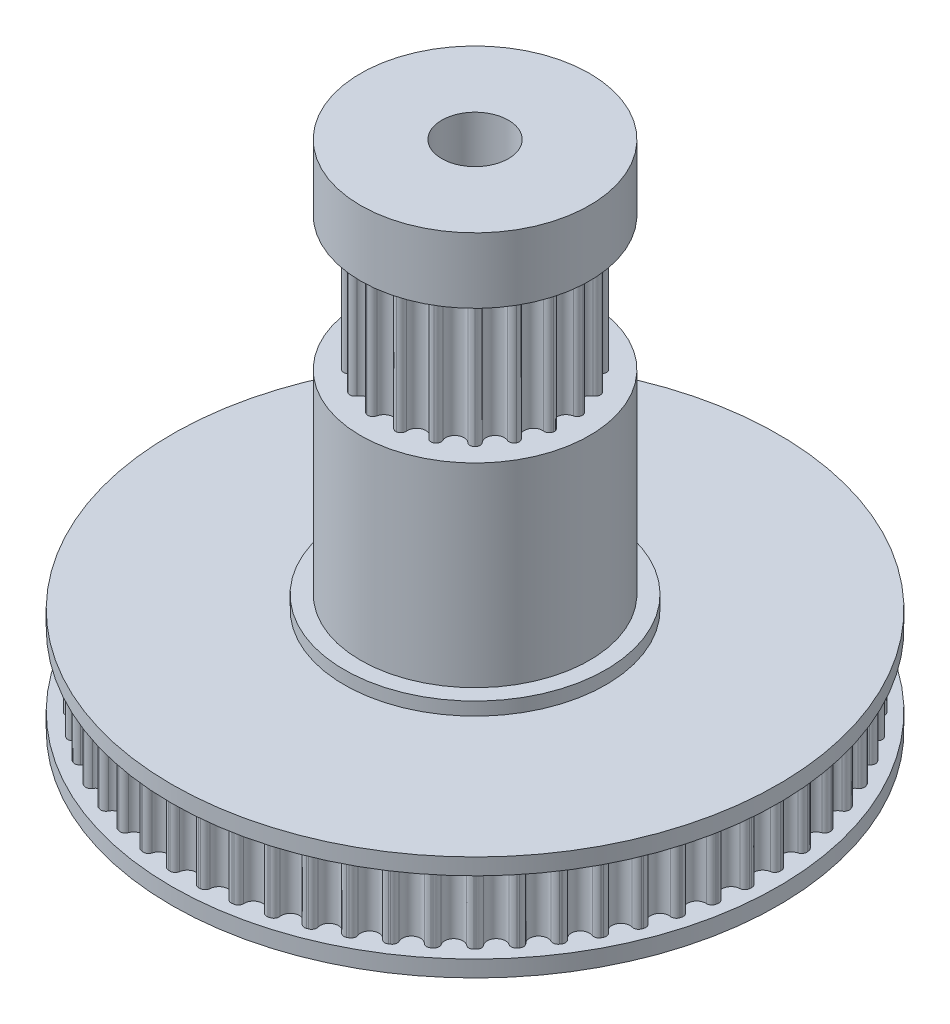
SolidWorks part; units mm, degrees
ref_plane "Front Plane" through (0, 0, 0) normal (0, 0, 1) x (1, 0, 0)
ref_plane "Top Plane" through (0, 0, 0) normal (0, 1, 0) x (1, 0, 0)
ref_plane "Right Plane" through (0, 0, 0) normal (1, 0, 0) x (0, 0, -1)
sketch "PulleyOffsets" plane through (0, 0, 0) normal (1, 0, 0) x (0, 0, -1)
  line L0 (15.875, 0) -> (-15.875, 0) construction
  line L1 (15.875, 31.75) -> (-15.875, 31.75) construction
  line L2 (0, 0) -> (0, 31.75) construction
  point P7 (0, 0)
  dimension "D1" = 31.75
ref_axis "Axis1" through (0, 34.9332, 0) along (0, -1, 0)
ref_plane "Big Pulley Plane" through (0, 0, 0) normal (0, 1, 0) x (1, 0, 0)
ref_plane "Small Pulley Plane" through (0, 31.75, 0) normal (0, 1, 0) x (1, 0, 0)
sketch "Sketch1" plane through (0, 0, 0) normal (0, 1, 0) x (1, 0, 0)
  line L0 (0, 0) -> (0, 28.2667) construction
  line L1 (0, 0) -> (2.9202, 27.7837) construction
  circle A0 centre (0, 0) radius 28.2667 construction
  circle A1 centre (0, 0) radius 27.0467 construction
  circle A2 centre (0, 27.9367) radius 0.89 construction
  circle A5 centre (2.9202, 27.7837) radius 0.89 construction
  arc A6 (0, 27.0467) -> (0.8804, 27.8061) centre (0, 27.9367) ccw
  arc A7 (0.8804, 27.8061) -> (1.3997, 28.2321) centre (1.3749, 27.7327) cw
  arc A8 (1.559, 28.2237) -> (2.031, 27.7458) centre (1.5314, 27.7245) cw
  arc A9 (2.8272, 26.8986) -> (2.031, 27.7458) centre (2.9202, 27.7837) cw
  arc A10 (1.3997, 28.2321) -> (1.559, 28.2237) centre (0, 0) cw
  arc A11 (0, 27.0467) -> (2.8272, 26.8986) centre (0, 0) ccw
  dimension "D1" = 56.5335
  dimension "D3" = 1.78
  dimension "D4" = 0.5
  dimension "D2" = 1.22
  dimension "D5" = 6
extrude "Boss-Extrude1" add sketch "Sketch1" along normal mid plane 7.112 contours A6 A11 A9 A8 A7 region at (0.001, 0, -0.0192)
pattern_circular "CirPattern1" count 60 over 360 about axis through (0, 34.9332, 0) along (0, -1, 0) of "Boss-Extrude1"
sketch "Sketch2" plane through (0, 0, 0) normal (1, 0, 0) x (0, 0, -1)
  line L10 (0, 3.5) -> (29.4415, 3.5) construction
  line L11 (0, 3.5) -> (0, 5.0875) construction
  line L12 (0, 5.0875) -> (29.4415, 5.0875) construction
  line L15 (29.4415, 3.5) -> (29.4415, 5.0875) construction
  line L20 (0, 34.9332) -> (0, -6.9932) construction
  line L22 (29.4415, 5.0875) -> (0, 5.0875)
  line L23 (29.4415, 5.0875) -> (29.4415, 3.5)
  line L24 (29.4415, 3.5) -> (0, 3.5)
  line L25 (0, 5.0875) -> (0, 3.5)
  dimension "D1" = 1.5875
  dimension "D2" = 29.4415
  dimension "D3" = 3.5
revolve "Revolve3" add sketch "Sketch2" angle 360 about axis through (0, 34.9332, 0) along (0, -1, 0) region at (0, 4.2937, -14.7207)
mirror "Mirror1" about plane through (0, 0, 0) normal (0, 1, 0) of "Revolve3"
sketch "Sketch3" plane through (0, 0, 0) normal (0, 1, 0) x (1, 0, 0)
  circle A0 centre (0, 0) radius 22.225
  dimension "D1" = 44.45
extrude "Cut-Extrude1" [suppressed] cut sketch "Sketch3" against normal through all both and the other way through all
sketch "Sketch6" plane through (0, 0, 0) normal (0, 1, 0) x (1, 0, 0)
  line L0 (0, 0) -> (0, 9.1676) construction
  line L1 (0, 0) -> (2.731, 8.405) construction
  circle A0 centre (0, 0) radius 9.1676 construction
  circle A1 centre (0, 0) radius 7.9476 construction
  circle A2 centre (0, 8.8376) radius 0.89 construction
  circle A5 centre (2.731, 8.405) radius 0.89 construction
  arc A6 (0, 7.9476) -> (0.8721, 8.6598) centre (0, 8.8376) ccw
  arc A7 (0.8721, 8.6598) -> (1.4405, 9.0537) centre (1.362, 8.5599) cw
  arc A8 (1.4277, 9.0557) -> (1.8466, 8.5054) centre (1.3498, 8.5618) cw
  arc A9 (2.4559, 7.5586) -> (1.8466, 8.5054) centre (2.731, 8.405) cw
  arc A10 (1.4405, 9.0537) -> (1.4277, 9.0557) centre (0, 0) cw construction
  arc A11 (0, 7.9476) -> (2.4559, 7.5586) centre (0, 0) ccw
  arc A12 (1.4405, 9.0537) -> (1.4277, 9.0557) centre (0, 0) cw
  dimension "D3" = 1.78
  dimension "D4" = 0.5
  dimension "D2" = 1.22
  dimension "D1" = 18.3352
  dimension "D5" = 18
extrude "Boss-Extrude2" add sketch "Sketch6" along normal mid plane 13 from surface contours A6 A11 A9 A8 A7 region at (0.0089, 0, -0.0564) starting at plane "Small Pulley Plane"
pattern_circular "CirPattern2" count 20 over 360 about axis through (0, 34.9332, 0) along (0, -1, 0) of "Boss-Extrude2"
sketch "Sketch4" plane through (0, 0, 0) normal (0, 0, 1) x (1, 0, 0)
  line L0 (12.7, 5.0875) -> (-12.7, 5.0875) construction
  line L1 (29.4415, 5.0875) -> (-29.4415, 5.0875) construction
  line L2 (-12.7, 5.0875) -> (-12.7, 6.3575)
  line L3 (-12.7, 6.3575) -> (-11.1125, 6.3575)
  line L4 (-11.1125, 6.3575) -> (-11.1125, 25.25)
  line L5 (0, 0) -> (0, 44.6) construction
  line L6 (11.1125, 6.3575) -> (11.1125, 25.25) construction
  line L7 (12.7, 6.3575) -> (11.1125, 6.3575) construction
  line L8 (12.7, 5.0875) -> (12.7, 6.3575) construction
  line L9 (-11.1125, 25.25) -> (11.1125, 25.25) construction
  line L10 (-12.7, 5.0875) -> (0, 5.0875)
  line L11 (0, 5.0875) -> (0, 25.25)
  line L12 (0, 25.25) -> (-11.1125, 25.25)
  line L13 (1.841, 25.25) -> (3.5054, 25.25) construction
  line L14 (0.8721, 38.25) -> (-0.8721, 38.25) construction
  line L15 (-11.1125, 44.6) -> (0, 44.6)
  line L16 (-11.1125, 44.6) -> (-11.1125, 38.25)
  line L17 (-11.1125, 38.25) -> (0, 38.25)
  line L18 (0, 44.6) -> (0, 38.25)
  line L19 (-11.1125, 25.25) -> (-11.1125, 38.25) construction
  point P14 (0, 5.0875)
  dimension "D1" = 1.27
  dimension "D2" = 25.4
  dimension "D3" = 22.225
  dimension "D4" = 6.35
revolve "Revolve4" add sketch "Sketch4" angle 360 about L11
sketch "Sketch7" plane through (0, 44.6, 0) normal (0, 1, 0) x (1, 0, 0)
  circle A0 centre (0, 0) radius 3.2385
  dimension "D1" = 6.477
extrude "Cut-Extrude2" cut sketch "Sketch7" against normal through all both and the other way through all
sketch "Sketch8" plane through (0, -5.0875, 0) normal (0, -1, 0) x (1, 0, 0)
  circle A0 centre (0, 0) radius 4.7625
  dimension "D1" = 9.525
equation "\"TEETH_NUM\"= 60"
equation "\"TOOTH_PITCH\"= 3mm"
equation "\"PITCH_LINE_OFFSET\"= .015in"
equation "\"DIAMETER_PER_GROOVE\"= \"OUTSIDE_DIAMETER\" / \"TEETH_NUM\" * 1in"
equation "\"PITCH_DIAMETER\"= ( ( \"TEETH_NUM\" * 3 - 1.31 ) / 3.1415 + .415 ) * 1mm"
equation "\"OUTSIDE_DIAMETER\"= \"PITCH_DIAMETER\" - \"PITCH_LINE_OFFSET\" * 2"
equation "\"D1@Sketch1\"=\"OUTSIDE_DIAMETER\""
equation "\"TOOTH_HEIGHT\"= 1.22mm"
equation "\"D2@Sketch1\"=\"TOOTH_HEIGHT\""
equation "\"TOOTH_DIAMETER\"= 1.78mm"
equation "\"INTERNAL_RADIUS\"= .5mm"
equation "\"D3@Sketch1\"=\"TOOTH_DIAMETER\""
equation "\"D5@Sketch1\"=360 / \"TEETH_NUM\""
equation "\"D4@Sketch1\"=\"INTERNAL_RADIUS\""
equation "\"D1@CirPattern1\"=\"TEETH_NUM\""
equation "\"BELT_GAP\"= 7mm"
equation "\"D2@Sketch2\"=\"PITCH_DIAMETER\"/2+1/32"
equation "\"D3@Sketch2\"=\"BELT_GAP\"/2"
equation "\"2_TEETH_NUM\"= 20"
equation "\"2_PITCH_DIAMETER\"= ( ( \"2_TEETH_NUM\" * 3 - 1.31 ) / 3.1415 + .415 ) * 1mm"
equation "\"2_OUTSIDE_DIAMETER\"= \"2_PITCH_DIAMETER\" - \"PITCH_LINE_OFFSET\" * 2"
equation "\"2_DIAMETER_PER_GROOVE\"= \"2_OUTSIDE_DIAMETER\" / \"2_TEETH_NUM\" * 1in"
equation "\"D5@Sketch6\"=360/\"2_TEETH_NUM\""
equation "\"D1@Sketch6\"=\"2_OUTSIDE_DIAMETER\""
equation "\"D2@Sketch6\"=\"TOOTH_HEIGHT\""
equation "\"D3@Sketch6\"=\"TOOTH_DIAMETER\""
equation "\"D4@Sketch6\"=\"INTERNAL_RADIUS\""
equation "\"2_BELT_GAP\"= 13mm"
equation "\"D1@CirPattern2\"=\"2_TEETH_NUM\""
equation "\"D1@Boss-Extrude2\"=\"2_BELT_GAP\""
equation "\"Pulley_OffSets\"= 1.25"
equation "\"D1@PulleyOffsets\" = \"Pulley_OffSets\""
